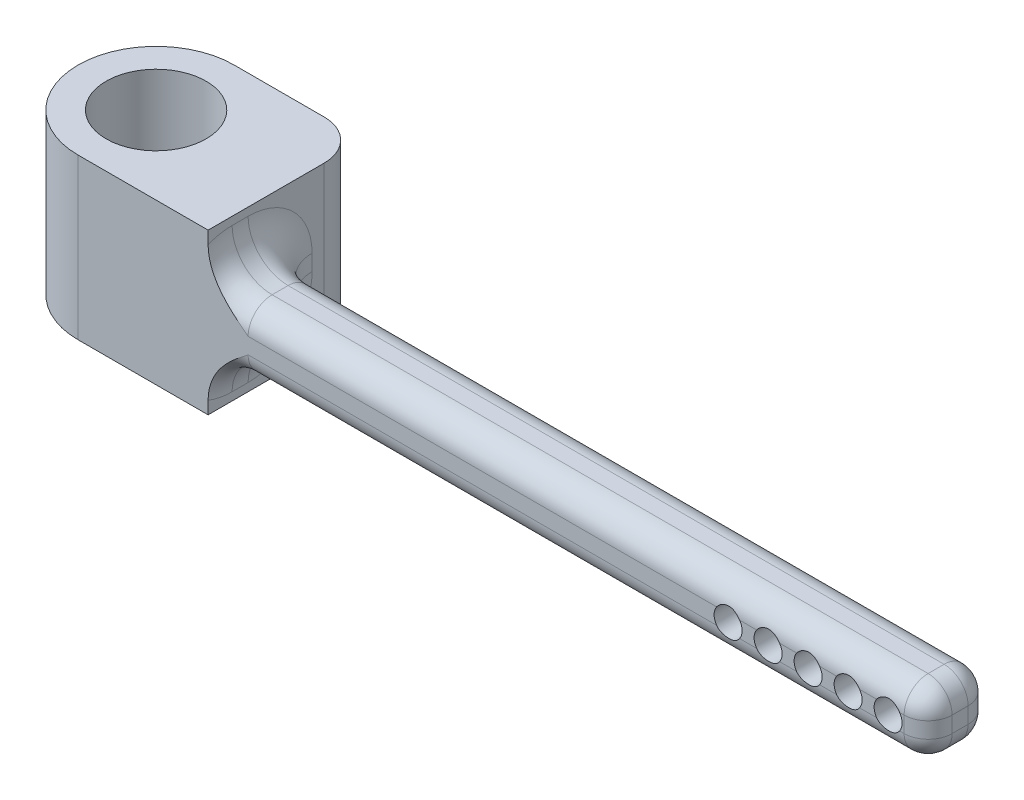
SolidWorks part; units mm, degrees
ref_plane "Front Plane" through (0, 0, 0) normal (0, 0, 1) x (1, 0, 0)
ref_plane "Top Plane" through (0, 0, 0) normal (0, 1, 0) x (1, 0, 0)
ref_plane "Right Plane" through (0, 0, 0) normal (1, 0, 0) x (0, 0, -1)
sketch "Sketch1" plane through (0, 0, 0) normal (0, 1, 0) x (1, 0, 0)
  line L0 (0, 9.75) -> (11.25, 9.75)
  line L1 (16.25, 4.75) -> (16.25, -9.75)
  line L2 (16.25, -9.75) -> (0, -9.75)
  circle A0 centre (0, 0) radius 6.25
  arc A1 (0, 9.75) -> (0, -9.75) centre (0, 0) ccw
  arc A2 (11.25, 9.75) -> (16.25, 4.75) centre (11.25, 4.75) cw
  dimension "D1" = 12.5
  dimension "D2" = 3.5
  dimension "D4" = 5
  dimension "D3" = 16.25
extrude "Boss-Extrude1" add sketch "Sketch1" along normal blind 20
sketch "Sketch2" plane through (16.25, 0, 0) normal (1, 0, 0) x (0, 0, -1)
  line L0 (-9.75, 20) -> (-9.75, 0) construction
  line L1 (-6.75, 6) -> (-4.75, 6)
  line L2 (-9.75, 9) -> (-9.75, 11)
  line L3 (-6.75, 14) -> (-4.75, 14)
  line L4 (-1.75, 9) -> (-1.75, 11)
  line L5 (-9.75, 10) -> (4.75, 10) construction
  line L6 (4.75, 20) -> (4.75, 0) construction
  arc A0 (-6.75, 6) -> (-9.75, 9) centre (-6.75, 9) cw
  arc A1 (-4.75, 6) -> (-1.75, 9) centre (-4.75, 9) ccw
  arc A2 (-4.75, 14) -> (-1.75, 11) centre (-4.75, 11) cw
  arc A3 (-9.75, 11) -> (-6.75, 14) centre (-6.75, 11) cw
  point P13 (-9.75, 6)
  dimension "D2" = 3
  dimension "D1" = 8
extrude "Boss-Extrude2" add sketch "Sketch2" along normal blind 90
sketch "Sketch3" plane through (0, 0, 1.75) normal (0, 0, -1) x (-1, 0, 0)
  line L0 (-106.25, 10) -> (-81.25, 10) construction
  line L1 (-106.25, 9) -> (-106.25, 11) construction
  circle A0 centre (-101.25, 10) radius 1.75
  circle A1 centre (-96.25, 10) radius 1.75
  circle A2 centre (-91.25, 10) radius 1.75
  circle A3 centre (-86.25, 10) radius 1.75
  circle A4 centre (-81.25, 10) radius 1.75
  dimension "D1" = 3.5
  dimension "D3" = 5
  dimension "D4" = 5
  dimension "D2" = 5
extrude "Cut-Extrude1" cut sketch "Sketch3" against normal through all
fillet "Fillet1" radius 3 8 edges at (106.25, 13.1213, 2.6287) (106.25, 14, 5.75) (106.25, 13.1213, 8.8713) (106.25, 10, 9.75) (106.25, 6.8787, 8.8713) (106.25, 6, 5.75) (106.25, 6.8787, 2.6287) (106.25, 10, 1.75)
fillet "Fillet2" radius 5 7 edges at (16.25, 6.8787, 8.8713) (16.25, 6, 5.75) (16.25, 13.1213, 8.8713) (16.25, 14, 5.75) (16.25, 13.1213, 2.6287) (16.25, 10, 1.75) (16.25, 6.8787, 2.6287)
